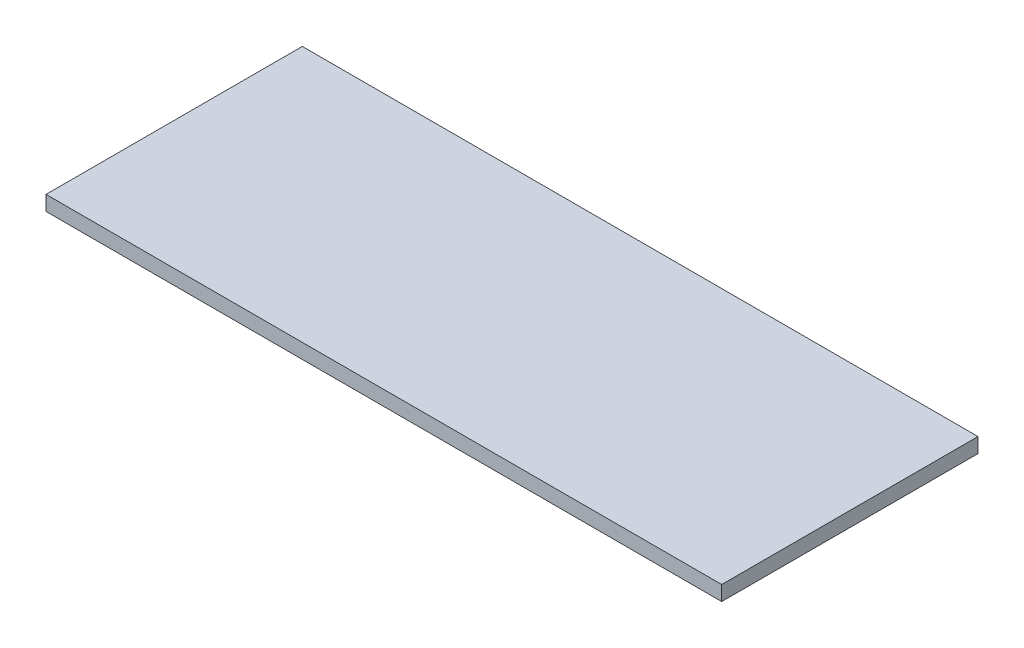
SolidWorks part; units mm, degrees
ref_plane "Front Plane" through (0, 0, 0) normal (0, 0, 1) x (1, 0, 0)
ref_plane "Top Plane" through (0, 0, 0) normal (0, 1, 0) x (1, 0, 0)
ref_plane "Right Plane" through (0, 0, 0) normal (1, 0, 0) x (0, 0, -1)
sketch "Sketch1" plane through (0, 0, 0) normal (0, 1, 0) x (1, 0, 0)
  line L0 (0, 0) -> (145, 55) construction
  line L1 (0, 0) -> (145, 0)
  line L2 (0, 0) -> (0, 55)
  line L3 (0, 55) -> (145, 55)
  line L4 (145, 0) -> (145, 55)
  point P5 (72.5, 27.5)
  dimension "D1" = 145
  dimension "D2" = 55
extrude "Boss-Extrude1" add sketch "Sketch1" along normal blind 3.175
ref_plane "Plane1" through (72.5, 0, 0) normal (1, 0, 0) x (0, 0, -1)
ref_plane "Plane2" through (0, 0, -27.5) normal (0, 0, -1) x (-1, 0, 0)
sketch "Sketch3" plane through (0, 3.175, 0) normal (0, 1, 0) x (1, 0, 0)
  line L0 (0, 0) -> (145, 55) construction
  point P4 (72.5, 27.5)
ref_axis "Axis1" through (72.5, 3.175, -27.5) along (0, 1, 0)
